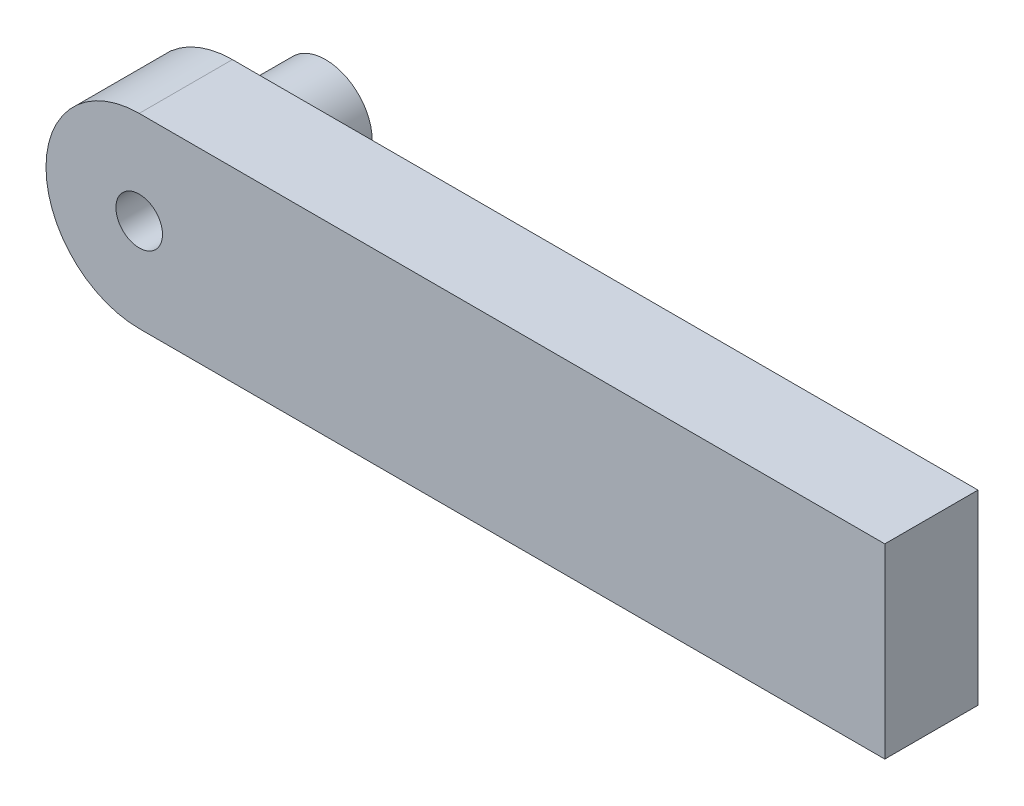
SolidWorks part; units mm, degrees
material "PET"
ref_plane "Piano frontale" through (0, 0, 0) normal (0, 0, 1) x (1, 0, 0)
ref_plane "Piano superiore" through (0, 0, 0) normal (0, 1, 0) x (1, 0, 0)
ref_plane "Piano destro" through (0, 0, 0) normal (1, 0, 0) x (0, 0, -1)
sketch "Schizzo1" plane through (0, 0, 0) normal (0, 0, 1) x (1, 0, 0)
  line L0 (20, 4.5035) -> (-20, 4.5035)
  line L2 (-20, -5.4965) -> (20, -5.4965)
  line L12 (20, 4.5035) -> (20, -5.4965)
  arc A0 (-20, 4.5035) -> (-20, -5.4965) centre (-20, -0.4965) ccw
  dimension "D1" = 10
  dimension "D9" = 40
extrude "Estrusione-Estrusione1" add sketch "Schizzo1" along normal blind 5
sketch "Schizzo2" plane through (0, 0, 0) normal (0, 0, -1) x (-1, 0, 0)
  arc A0 (20, -5.4965) -> (20, 4.5035) centre (20, -0.4965) ccw construction
  arc A1 (20, -5.4965) -> (20, 4.5035) centre (20, -0.4965) ccw construction
  circle A2 centre (20, -0.4965) radius 2.5
extrude "Estrusione-Estrusione2" add sketch "Schizzo2" along normal blind 5 contours A2
sketch "Schizzo3" plane through (0, 0, -5) normal (0, 0, -1) x (-1, 0, 0)
  circle A0 centre (20, -0.4965) radius 1.25
  dimension "D1" = 2.5
extrude "Taglio-Estrusione1" cut sketch "Schizzo3" against normal through all
ref_point "Punto1"
ref_axis "Assi1" through (-20, -0.4965, 5) along (0, 0, -1)
ref_axis "Assi2" through (20, 4.5035, 0) along (-1, 0, 0)
